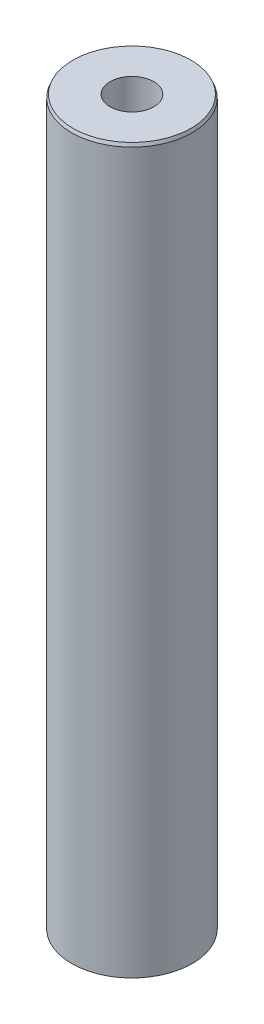
SolidWorks part; units mm, degrees
ref_plane "Front Plane" through (0, 0, 0) normal (0, 0, 1) x (1, 0, 0)
ref_plane "Top Plane" through (0, 0, 0) normal (0, 1, 0) x (1, 0, 0)
ref_plane "Right Plane" through (0, 0, 0) normal (1, 0, 0) x (0, 0, -1)
sketch "Sketch1" plane through (0, 0, 0) normal (0, 1, 0) x (1, 0, 0)
  circle A0 centre (0, 0) radius 50
  dimension "SHAFT_OD" = 100
extrude "Boss-Extrude1" add sketch "Sketch1" along normal blind 600
sketch "Sketch2" plane through (0, 0, 0) normal (0, 1, 0) x (1, 0, 0)
  circle A0 centre (0, 0) radius 18.0935
  dimension "BORE_D" = 36.187
extrude "Cut-Extrude1" cut sketch "Sketch2" along normal through all
chamfer "Chamfer1" distance 2.6544 angle 21.628 2 edges at (0, 600, 50) (0, 0, 50) first distance on face at (0, 600, 50) first distance on face at (0, 0, 18.0935)
